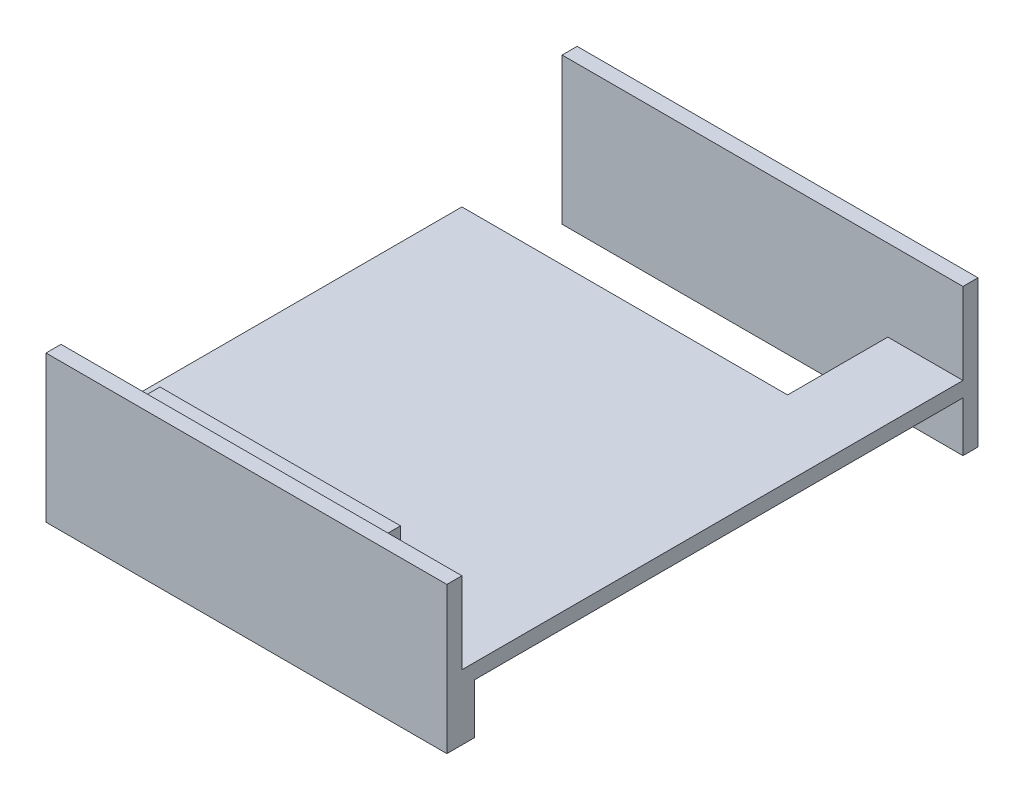
SolidWorks part; units mm, degrees
ref_plane "前视基准面" through (0, 0, 0) normal (0, 0, 1) x (1, 0, 0)
ref_plane "上视基准面" through (0, 0, 0) normal (0, 1, 0) x (1, 0, 0)
ref_plane "右视基准面" through (0, 0, 0) normal (1, 0, 0) x (0, 0, -1)
other "Configuration Table"
sketch "草图1" plane through (0, 0, 0) normal (0, 1, 0) x (1, 0, 0)
  line L1 (32, 0) -> (32, 40)
  line L3 (0, 40) -> (0, 0)
  line L4 (0, -1.2) -> (0, 0)
  line L5 (0, -1.2) -> (32, -1.2)
  line L6 (32, -1.2) -> (32, 0)
  line L7 (0, 40) -> (0, 41.2)
  line L8 (0, 41.2) -> (32, 41.2)
  line L9 (32, 41.2) -> (32, 40)
extrude "凸台-拉伸-中间层" add sketch "草图1" along normal blind 1.2
sketch "草图2" plane through (0, 1.2, 0) normal (0, 1, 0) x (1, 0, 0)
  line L0 (0, 0) -> (0, -1.2)
  line L1 (0, -1.2) -> (32, -1.2)
  line L2 (32, -1.2) -> (32, 0)
  line L3 (32, -1.2) -> (32, 41.2) construction
  line L4 (32, 0) -> (0, 0)
  line L5 (0, 41.2) -> (32, 41.2)
  line L6 (32, 41.2) -> (32, 40)
  line L7 (32, 40) -> (0, 40)
  line L8 (0, 41.2) -> (0, -1.2) construction
  line L9 (0, 40) -> (0, 41.2)
extrude "凸台-拉伸-PCB侧上下挡板" add sketch "草图2" along normal blind 6.5
sketch "草图3" plane through (0, 1.2, 0) normal (0, 1, 0) x (1, 0, 0)
  line L0 (32, 0) -> (0, 0) construction
  line L1 (16, 0) -> (25.6, 0)
  line L2 (32, 0) -> (0, 0) construction
  line L3 (25.6, 0) -> (25.6, 1.5)
  line L4 (16, 0) -> (6.4, 0)
  line L5 (6.4, 0) -> (6.4, 1.5)
  line L6 (6.4, 1.5) -> (25.6, 1.5)
  point P0 (16, 0)
extrude "凸台-拉伸-PCB侧下方卡槽" add sketch "草图3" along normal blind 6
sketch "草图4" plane through (0, 1.2, 0) normal (0, 1, 0) x (1, 0, 0)
  line L0 (0, 40) -> (32, 40) construction
  line L1 (16, 40) -> (26, 40)
  line L2 (0, 40) -> (32, 40) construction
  line L3 (16, 40) -> (0, 40)
  line L4 (0, 40) -> (0, 32)
  line L5 (0, 32) -> (26, 32)
  line L6 (26, 32) -> (26, 40)
  point P0 (16, 40)
  point P10 (0, 0)
extrude "切除-拉伸-穿线孔" cut sketch "草图4" against normal up to next
sketch "草图5" plane through (0, 0, 0) normal (0, -1, 0) x (1, 0, 0)
  line L0 (0, 1.2) -> (0, 0)
  line L3 (0, -40) -> (32, -40)
  line L5 (32, 0) -> (32, 1.2)
  line L6 (32, 1.2) -> (0, 1.2)
  line L7 (0, -40) -> (0, -41.2)
  line L8 (0, -41.2) -> (32, -41.2)
  line L9 (32, -41.2) -> (32, -40)
  line L10 (32, 1.2) -> (32, -41.2) construction
  line L11 (32, -1) -> (0, -1)
  line L12 (0, -32) -> (0, 1.2) construction
  line L13 (0, -1) -> (0, 0)
  line L14 (32, 0) -> (32, -1)
  point P24 (32, -1)
extrude "凸台-拉伸-电池侧上下挡板" add sketch "草图5" along normal blind 4
